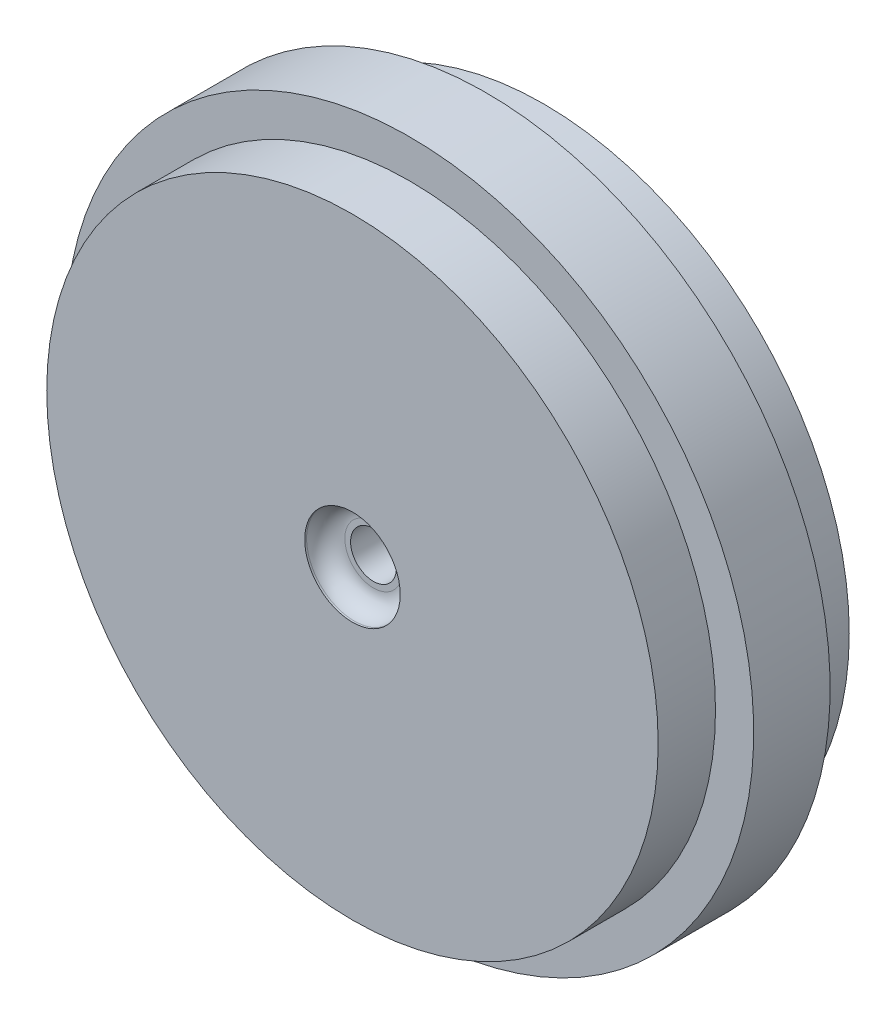
SolidWorks part; units mm, degrees
material "PET"
ref_plane "Plan de face" through (0, 0, 0) normal (0, 0, 1) x (1, 0, 0)
ref_plane "Plan de dessus" through (0, 0, 0) normal (0, 1, 0) x (1, 0, 0)
ref_plane "Plan de droite" through (0, 0, 0) normal (1, 0, 0) x (0, 0, -1)
sketch "Esquisse1" plane through (0, 0, 0) normal (0, 0, 1) x (1, 0, 0)
  circle A0 centre (0, 0) radius 14.5
  dimension "D1" = 29
extrude "Boss.-Extru.1" add sketch "Esquisse1" along normal blind 10
sketch "Esquisse2" plane through (0, 0, 0) normal (0, 0, 1) x (1, 0, 0)
  circle A0 centre (0, 0) radius 16.5
  dimension "D1" = 33
extrude "Boss.-Extru.2" add sketch "Esquisse2" along normal offset from surface (8 mm away) 1 from offset 1 up to face at (14.5, 0, 10)
sketch "Esquisse6" plane through (0, 0, 10) normal (0, 0, 1) x (1, 0, 0)
  circle A0 centre (0, 0) radius 13.5
  dimension "D1" = 27
extrude "Enlèv. mat.-Extru.4" cut sketch "Esquisse6" against normal blind 1
hole_wizard "Chambrage pour vis à tête ronde bombée M21" positions "Esquisse9" profile "Esquisse8" counterbore size "M2" standard "Ansi Metric" end condition through all
sketch "Esquisse9" plane through (0, 0, 9) normal (0, 0, 1) x (1, 0, 0)
  point P0 (0, 0)
sketch "Esquisse8" plane through (0, 0, 9) normal (1, 0, 0) x (0, -1, 0)
  line L0 (0, 0) -> (0, 9)
  line L1 (0, 9) -> (1.2, 9)
  line L3 (1.2, 9) -> (1.2, 1.6)
  line L4 (1.2, 1.6) -> (2.5, 1.6)
  line L5 (2.5, 1.6) -> (2.5, 0)
  line L7 (2.5, 0) -> (0, 0)
  line L11 (0, -6.35) -> (0, 107.95) construction
  dimension "Diamètre du perçage jusqu'au prochain" = 2.4
  dimension "Profondeur du perçage jusqu'au prochain" = 9
  dimension "Diamètre du chambrage" = 5
  dimension "Profondeur du chambrage" = 1.6
sketch "Esquisse13" plane through (0, 0, 0) normal (0, 0, -1) x (-1, 0, 0)
  circle A0 centre (0, 0) radius 13.5
  circle A1 centre (0, 0) radius 4.2
  dimension "D1" = 27
  dimension "D2" = 8.4
extrude "Enlèv. mat.-Extru.7" cut sketch "Esquisse13" against normal offset from surface (7 mm away) 2 up to face at (2.5, 0, 9)
sketch "Esquisse15" plane through (0, 0, 0) normal (0, 0, -1) x (-1, 0, 0)
  line L0 (-2.15, 2.0922) -> (-2.15, -2.0922)
  line L1 (2.15, 2.0922) -> (2.15, -2.0922)
  arc A0 (-2.15, -2.0922) -> (2.15, -2.0922) centre (0, 0) ccw
  arc A1 (2.15, 2.0922) -> (-2.15, 2.0922) centre (0, 0) ccw
  dimension "D1" = 6
  dimension "D2" = 2.15
  dimension "D3" = 2.15
extrude "Enlèv. mat.-Extru.8" cut sketch "Esquisse15" against normal blind 7
sketch "Sketch2" plane through (0, 0, 1) normal (0, 0, -1) x (-1, 0, 0)
  circle A0 centre (0, 0) radius 16.5
  circle A1 centre (0, 0) radius 14.5
extrude "Boss-Extrude2" add sketch "Sketch2" along normal up to surface (1 mm away) and the other way up to surface (9 mm away) up to face at (0, 0, 0) other way up to face at (13.5, 0, 10)
sketch "Sketch3" plane through (0, 0, 0) normal (0, 0, -1) x (-1, 0, 0)
  circle A0 centre (0, 0) radius 16.5
  circle A1 centre (0, 0) radius 22.5
  dimension "D1" = 6
extrude "Boss-Extrude3" add sketch "Sketch3" against normal up to surface (10 mm away) up to face at (13.5, 0, 10)
fillet "Fillet1" radius 1 2 edges at (-22.5, 0, 0) (22.5, 0, 10)
ref_plane "Plane1" through (0, 0, 0) normal (1, 0, 0) x (0, 0, -1)
sketch "Sketch4" plane through (0, 0, 0) normal (1, 0, 0) x (0, 0, -1)
  line L0 (-9, 22.5) -> (-1, 22.5) construction
  line L1 (-1, 22.5) -> (-9, 22.5) construction
  line L2 (-9, 22.5) -> (-9, 18)
  line L3 (-5, 22.5) -> (-5, 24.473) construction
  line L4 (-9, 18) -> (-1, 18)
  line L5 (-1, 18) -> (-1, 22.5)
  arc A0 (-9, 22.5) -> (-1, 22.5) centre (-5, 14.0611) cw
  point P10 (-5, 23.4)
  dimension "D2" = 0.9
extrude "Boss-Extrude4" add sketch "Sketch4" along normal blind 0.5 and the other way blind 0.5
pattern_circular "CirPattern1" count 70 over 360 about axis through (0, 0, 73.6396) along (0, 0, -1) of "Boss-Extrude4"
sketch "Sketch5" plane through (0, 0, 0) normal (0, 0, -1) x (-1, 0, 0)
  circle A0 centre (0, 0) radius 16
  circle A1 centre (0, 0) radius 40
  dimension "D1" = 32
  dimension "D2" = 80
extrude "Cut-Extrude1" cut sketch "Sketch5" against normal blind 20
sketch "Sketch6" plane through (0, 0, 0) normal (0, 0, -1) x (-1, 0, 0)
  circle A0 centre (0, 0) radius 16
  circle A1 centre (0, 0) radius 18
  circle A2 centre (0, 0) radius 16 construction
  dimension "D1" = 2
extrude "Boss-Extrude5" add sketch "Sketch6" against normal blind 4 from offset 3 offset against normal yes
sketch "Sketch8" plane through (0, 0, 9) normal (0, 0, 1) x (1, 0, 0)
  circle A0 centre (0, 0) radius 13.5
  circle A1 centre (0, 0) radius 2.5
  circle A2 centre (0, 0) radius 13.5 construction
  circle A3 centre (0, 0) radius 2.5 construction
extrude "Boss-Extrude6" add sketch "Sketch8" along normal up to surface (1 mm away) up to face at (13.5, 0, 10)
sketch "Sketch9" plane through (0, 0, 7.4) normal (0, 0, 1) x (1, 0, 0)
  circle A0 centre (0, 0) radius 2.5
  circle A1 centre (0, 0) radius 1.2
  circle A2 centre (0, 0) radius 1.2 construction
  circle A3 centre (0, 0) radius 2.5 construction
extrude "Boss-Extrude7" add sketch "Sketch9" along normal blind 1.5
fillet "Fillet2" radius 1 1 edges at (2.5, 0, 8.9)
